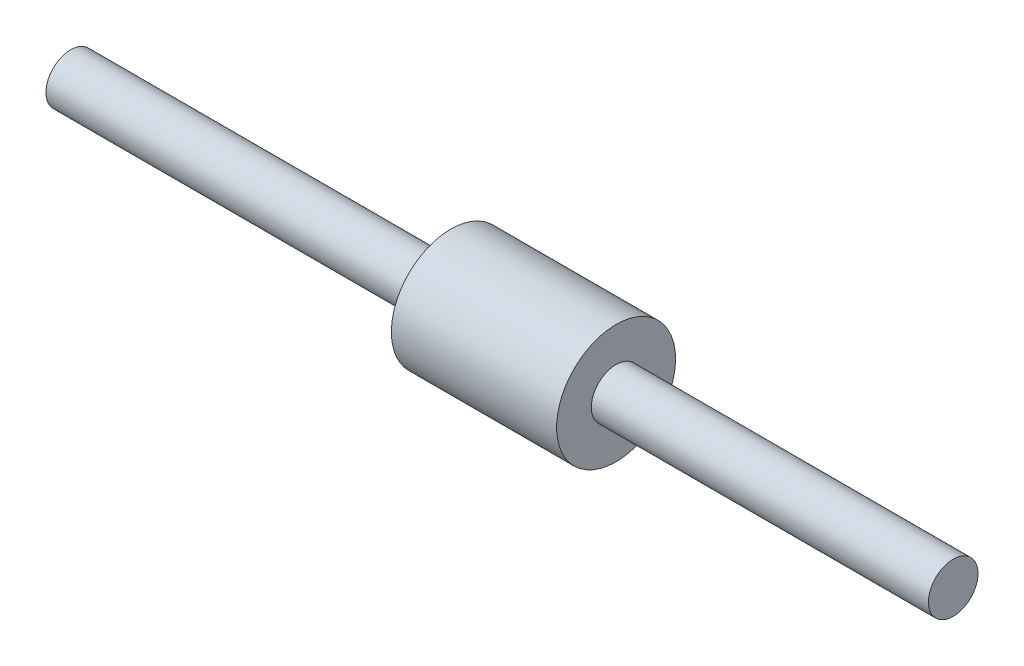
SolidWorks part; units mm, degrees
ref_plane "Front Plane" through (0, 0, 0) normal (0, 0, 1) x (1, 0, 0)
ref_plane "Top Plane" through (0, 0, 0) normal (0, 1, 0) x (1, 0, 0)
ref_plane "Right Plane" through (0, 0, 0) normal (1, 0, 0) x (0, 0, -1)
sketch "Sketch1" plane through (0, 0, 0) normal (0, 0, 1) x (1, 0, 0)
  line L0 (196.3562, 0) -> (-196.3562, 0) construction
  line L3 (127, 7.5) -> (-140, 7.5)
  line L4 (0, -42.6677) -> (0, 42.6677) construction
  line L7 (127, 7.5) -> (127, 0)
  line L8 (127, 0) -> (-127, 0)
  line L9 (-140, 7.5) -> (-140, 5.5)
  line L10 (-140, 5.5) -> (-127, 5.5)
  line L11 (-127, 5.5) -> (-127, 0)
  line L12 (-25, 18) -> (25, 18)
  line L13 (-25, 18) -> (-25, 7.5)
  line L14 (25, 18) -> (25, 7.5)
  point P3 (0, 18)
  point P10 (0, 0)
  dimension "D1" = 127
  dimension "D2" = 140
  dimension "D3" = 13
  dimension "D4" = 15
  dimension "D5" = 11
  dimension "D6" = 36
  dimension "D7" = 50
revolve "Revolve1" add sketch "Sketch1" angle 360 about L0 region at (-1.7975, 3.787, 0) region at (0, 12.75, 0)
